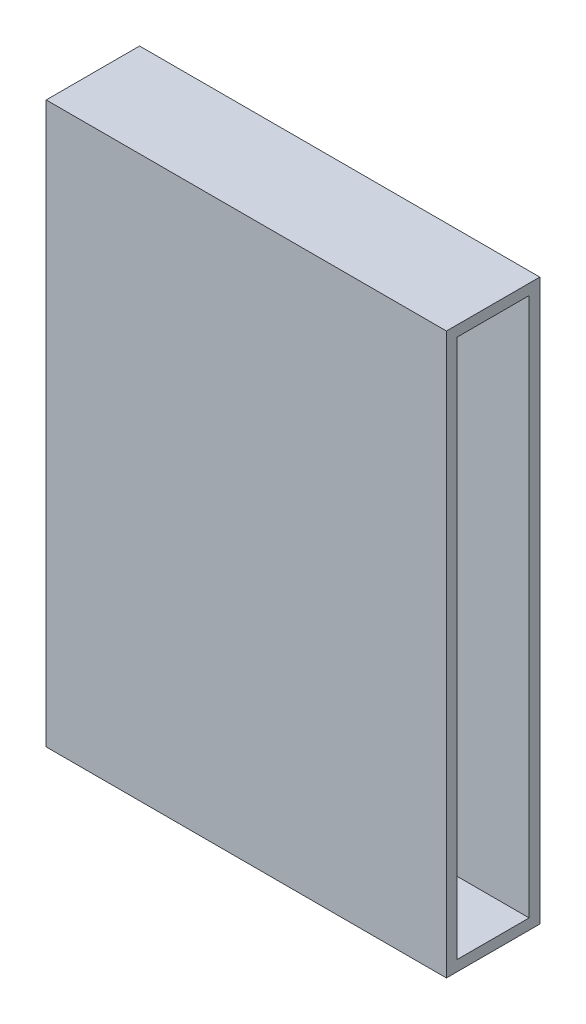
SolidWorks part; units mm, degrees
ref_plane "Top Plane" through (0, 0, 0) normal (0, 0, 1) x (1, 0, 0)
ref_plane "Front Plane" through (0, 0, 0) normal (0, 1, 0) x (1, 0, 0)
ref_plane "Right Plane" through (0, 0, 0) normal (1, 0, 0) x (0, 0, -1)
sketch "Sketch1" plane through (0, 0, 0) normal (0, 0, 1) x (1, 0, 0)
  line L1 (0, 0) -> (30, 0)
  line L2 (0, 0) -> (0, 42)
  line L3 (0, 42) -> (30, 42)
  line L4 (30, 0) -> (30, 42)
  dimension "D1" = 42
  dimension "D2" = 30
extrude "Boss-Extrude1" add sketch "Sketch1" along normal blind 7
sketch "Sketch2" plane through (0, 0, 0) normal (-1, 0, 0) x (0, 0, 1)
  line L14 (0.8, 41.2) -> (0.8, 0.8)
  line L15 (0.8, 0.8) -> (6.2, 0.8)
  line L16 (6.2, 0.8) -> (6.2, 41.2)
  line L17 (6.2, 41.2) -> (0.8, 41.2)
  line L18 (0.8, 41.2) -> (0.8, 0.8)
  line L19 (0.8, 0.8) -> (6.2, 0.8)
  line L20 (6.2, 0.8) -> (6.2, 41.2)
  line L21 (6.2, 41.2) -> (0.8, 41.2)
  dimension "D1" = 0.8
extrude "Cut-Extrude1" cut sketch "Sketch2" against normal through all
sketch "Sketch3" plane through (30, 0, 0) normal (1, 0, 0) x (0, 0, -1)
  line L0 (-7, 0) -> (-7, 42) construction
  line L1 (-6.2, 37) -> (-0.8, 37)
  line L2 (-6.2, 37) -> (-6.2, 5)
  line L3 (-6.2, 5) -> (-0.8, 5)
  line L4 (-0.8, 37) -> (-0.8, 5)
  line L6 (0, 0) -> (0, 42) construction
  point P6 (-6.2, 21)
  point P7 (0, 21)
  dimension "D1" = 32
  dimension "D2" = 0.8
  dimension "D3" = 0.8
  dimension "D4" = 0
